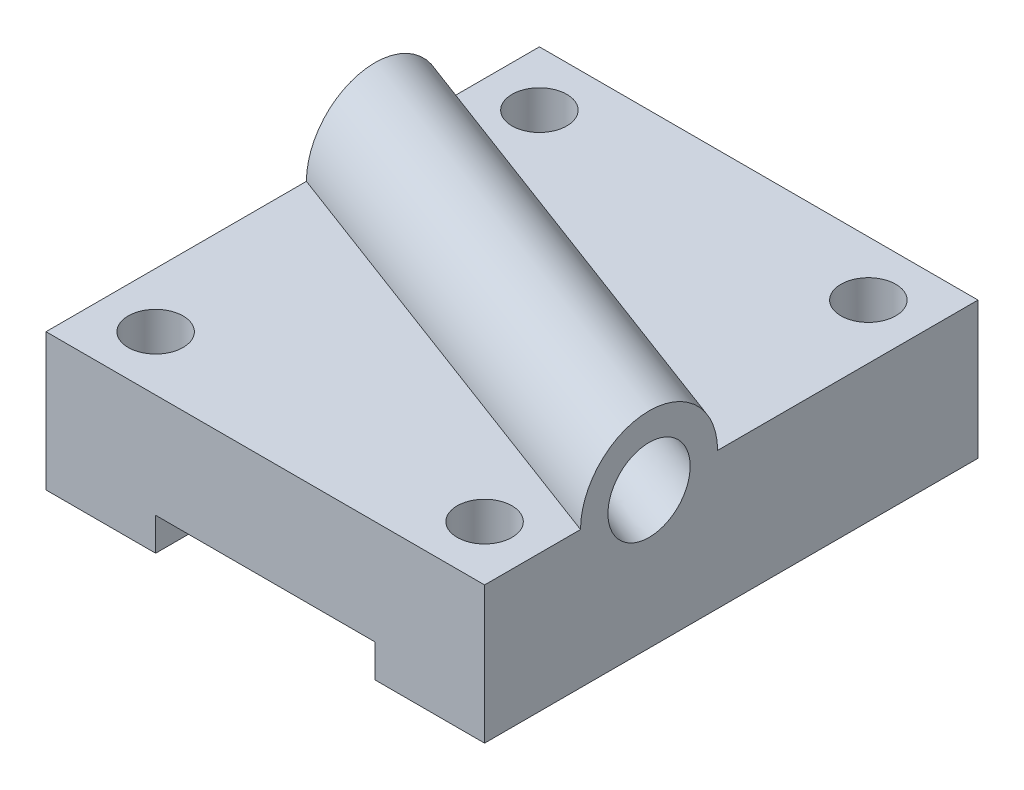
SolidWorks part; units mm, degrees
ref_plane "Alzado" through (0, 0, 0) normal (0, 0, 1) x (1, 0, 0)
ref_plane "Planta" through (0, 0, 0) normal (0, 1, 0) x (1, 0, 0)
ref_plane "Vista lateral" through (0, 0, 0) normal (1, 0, 0) x (0, 0, -1)
sketch "Croquis2" plane through (0, 0, 0) normal (0, 0, 1) x (1, 0, 0)
  line L0 (0, 0) -> (0, 25)
  line L1 (0, 25) -> (-80, 25)
  line L2 (-80, 25) -> (-80, 0)
  line L3 (-80, 0) -> (-60, 0)
  line L4 (-60, 0) -> (-60, 6)
  line L5 (-60, 6) -> (-20, 6)
  line L6 (-20, 6) -> (-20, 0)
  line L7 (-20, 0) -> (0, 0)
  dimension "D1" = 80
  dimension "D2" = 25
  dimension "D3" = 6
  dimension "D4" = 40
extrude "Saliente-Extruir1" add sketch "Croquis2" against normal blind 90
sketch "Croquis3" plane through (0, 25, 0) normal (0, 1, 0) x (1, 0, 0)
  line L0 (0, 90) -> (0, 0) construction
  line L1 (0, 0) -> (-80, 0) construction
  line L2 (-80, 90) -> (-80, 0) construction
  line L3 (0, 90) -> (-80, 90) construction
  circle A1 centre (-70, 80) radius 5
  circle A2 centre (-10, 80) radius 5
  circle A3 centre (-10, 10) radius 5
  circle A4 centre (-70, 10) radius 5
  point P6 (-10.9389, 80)
  point P17 (-70, 10)
  dimension "D3" = 10
  dimension "D1" = 10
  dimension "D2" = 10
  dimension "D6" = 10
  dimension "D7" = 10
  dimension "D8" = 10
  dimension "D4" = 2
  dimension "D5" = 2
extrude "Cortar-Extruir1" cut sketch "Croquis3" against normal up to next
sketch "Croquis4" plane through (0, 0, 0) normal (1, 0, 0) x (0, 0, -1)
  line L0 (90, 25) -> (0, 25) construction
  line L1 (0, 0) -> (0, 25) construction
  line L2 (42.5, 25) -> (17.5, 25)
  arc A0 (42.5, 25) -> (17.5, 25) centre (30, 25) ccw
  point P4 (31.5503, 25)
  dimension "D1" = 25
  dimension "D2" = 30
sketch "Croquis5" plane through (-80, 0, 0) normal (-1, 0, 0) x (0, 0, 1)
  line L0 (-90, 25) -> (0, 25) construction
  line L1 (-90, 25) -> (-90, 0) construction
  line L2 (-72.5, 25) -> (-47.5, 25)
  arc A0 (-47.5, 25) -> (-72.5, 25) centre (-60, 25) ccw
  dimension "D1" = 25
  dimension "D2" = 30
loft "Recubrir1" add profiles "Croquis5", "Croquis4" connector at (-80, 25, -72.5) connector at (0, 25, -42.5)
sketch "Croquis6" plane through (0, 0, 0) normal (1, 0, 0) x (0, 0, -1)
  circle A0 centre (30, 25) radius 7.5
  arc A2 (42.5, 25) -> (17.5, 25) centre (30, 25) ccw construction
  point P2 (0, 0)
  point P6 (0, 0)
  point P7 (0, 0)
  point P10 (0, 0)
  dimension "D1" = 15
sketch "Croquis7" plane through (-80, 0, 0) normal (-1, 0, 0) x (0, 0, 1)
  circle A0 centre (-60, 25) radius 7.5
  arc A1 (-47.5, 25) -> (-72.5, 25) centre (-60, 25) ccw construction
  dimension "D1" = 15
loft "Cortar-Recubrir1" cut profiles "Croquis7", "Croquis6" connector at (-80, 27.8178, -66.9505) connector at (0, 31.3775, -33.9468)
